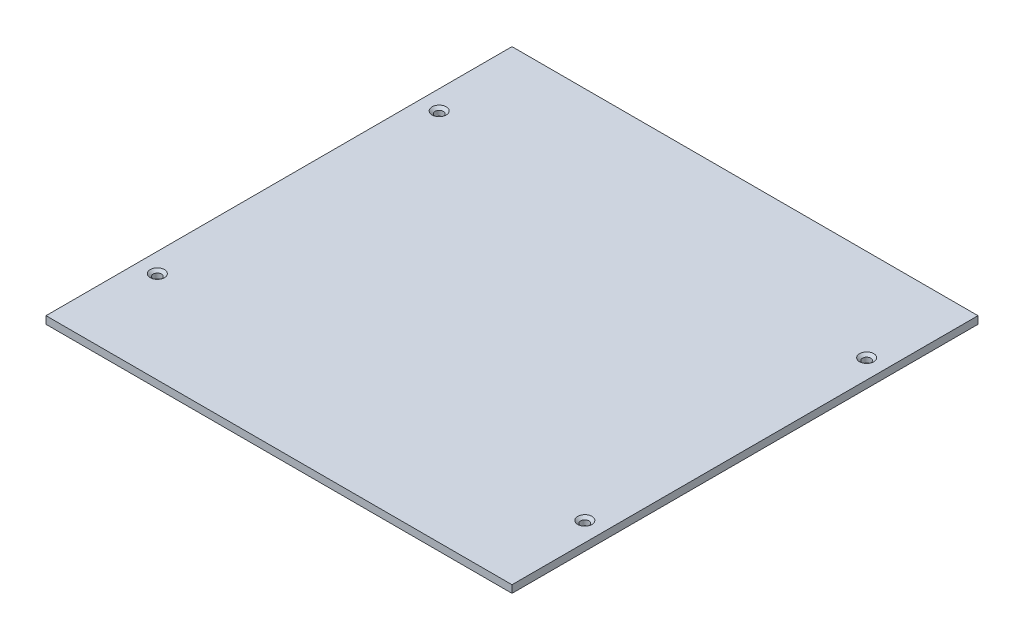
SolidWorks part; units mm, degrees
material "6061-T4 (SS)"
ref_plane "Front Plane" through (0, 0, 0) normal (0, 0, 1) x (1, 0, 0)
ref_plane "Top Plane" through (0, 0, 0) normal (0, 1, 0) x (1, 0, 0)
ref_plane "Right Plane" through (0, 0, 0) normal (1, 0, 0) x (0, 0, -1)
sketch "Sketch1" plane through (0, 0, 0) normal (0, 1, 0) x (1, 0, 0)
  line L1 (0, 0) -> (99.2004, 0)
  line L2 (0, 0) -> (0, 99.2004)
  line L3 (0, 99.2004) -> (99.2004, 99.2004)
  line L4 (99.2004, 0) -> (99.2004, 99.2004)
  dimension "D1" = 99.2004
  dimension "D2" = 99.2004
extrude "Boss-Extrude1" add sketch "Sketch1" along normal blind 1.6002
sketch "Sketch3" plane through (0, 1.6002, 0) normal (0, 1, 0) x (1, 0, 0)
  line L0 (0, 0) -> (1.6002, 0) construction
  line L1 (0, 0) -> (99.2004, 0) construction
  line L2 (1.6002, 0) -> (1.6002, 99.2004) construction
  line L3 (99.2004, 99.2004) -> (0, 99.2004) construction
  line L4 (0, 97.6002) -> (1.6002, 97.6002) construction
  line L5 (0, 99.2004) -> (0, 0) construction
  line L6 (1.6002, 97.6002) -> (97.6002, 97.6002) construction
  line L7 (97.6002, 97.6002) -> (97.6002, 99.2004) construction
  line L8 (97.6002, 97.6002) -> (97.6002, 0) construction
  line L9 (99.2004, 0) -> (99.2004, 99.2004) construction
  line L10 (49.6002, 97.6002) -> (49.6002, 49.6002) construction
  line L11 (95.1002, 49.6002) -> (4.1002, 49.6002) construction
  line L12 (4.1002, 49.6002) -> (4.1002, 79.6002) construction
  line L13 (4.1002, 49.6002) -> (4.1002, 19.6002) construction
  line L14 (95.1002, 49.6002) -> (95.1002, 19.6002) construction
  line L15 (95.1002, 49.6002) -> (95.1002, 79.6002) construction
  line L16 (1.6002, 1.6002) -> (97.6002, 1.6002) construction
  line L17 (49.6002, 49.6002) -> (49.6002, 1.6002) construction
  dimension "D1" = 1.6002
  dimension "D2" = 1.6002
  dimension "D3" = 1.6002
  dimension "D4" = 2.5
  dimension "D5" = 30
  dimension "D6" = 1.6002
hole_wizard "CSK for #0 Flat Head Machine Screw (100)1" positions "Sketch4" profile "Sketch5" countersink size "#0" standard "ANSI Inch" end condition through all
sketch "Sketch4" plane through (0, 1.6002, 0) normal (0, 1, 0) x (1, 0, 0)
  point P0 (4.1002, 79.6002)
  point P3 (4.1002, 19.6002)
  point P6 (95.1002, 19.6002)
  point P9 (95.1002, 79.6002)
sketch "Sketch5" plane through (4.1002, 1.6002, -79.6002) normal (1, 0, 0) x (0, 0, 1)
  line L0 (0, 0) -> (0, 1.6002)
  line L1 (0, 1.6002) -> (0.889, 1.6002)
  line L2 (0.889, 1.6002) -> (0.889, 0.5222)
  line L3 (0.889, 0.5222) -> (1.5113, 0)
  line L5 (1.5113, 0) -> (0, 0)
  line L6 (-0.889, 0.5222) -> (-1.5113, 0) construction
  line L11 (0, -6.35) -> (0, 107.95) construction
  dimension "Thru Hole Dia." = 1.778
  dimension "Thru Hole Depth" = 1.6002
  dimension "Near C'Sink Dia." = 3.0226
  dimension "Near C'Sink Angle" = 100
